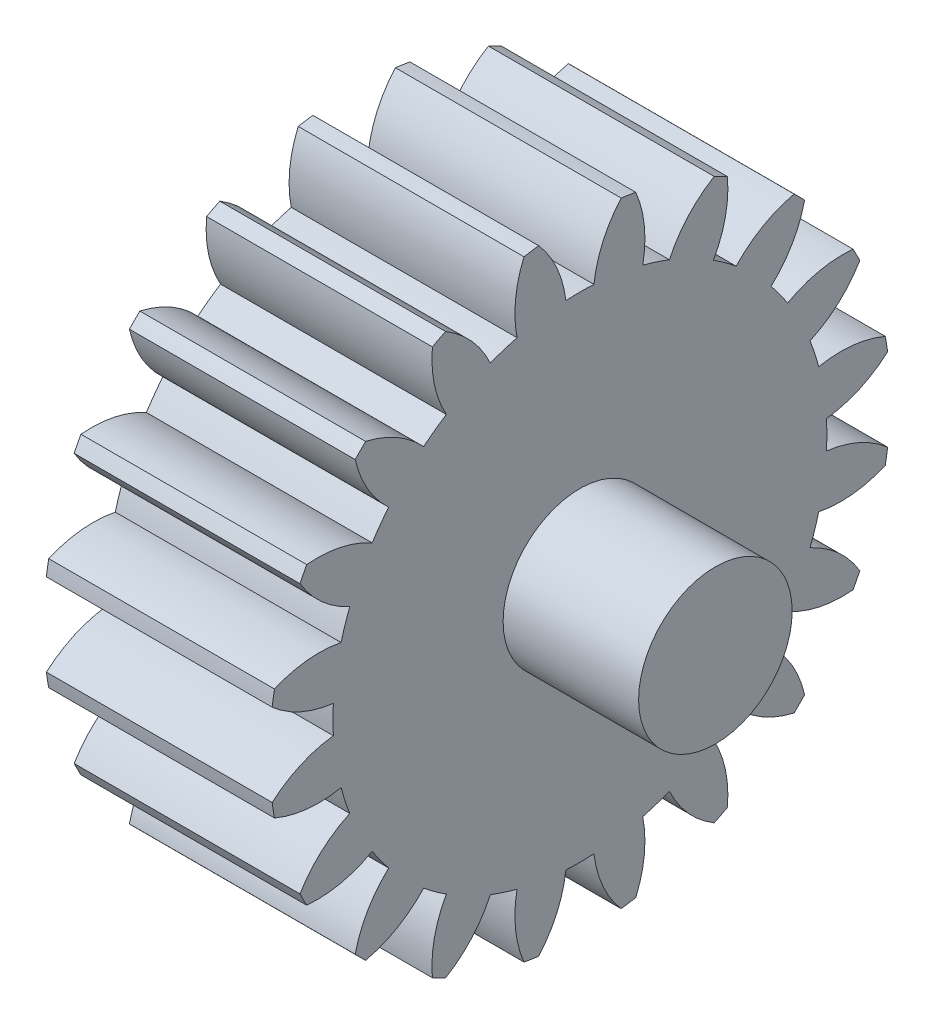
SolidWorks part; units mm, degrees
ref_plane "Plane1" through (0, 0, 0) normal (0, 0, 1) x (1, 0, 0)
ref_plane "Plane2" through (0, 0, 0) normal (0, 1, 0) x (1, 0, 0)
ref_plane "Plane3" through (0, 0, 0) normal (1, 0, 0) x (0, 0, -1)
sketch "HoldingSke" plane through (0, 0, 0) normal (0, 1, 0) x (1, 0, 0)
  line L0 (0, 0) -> (0.7518, -0.2736)
  line L1 (-15, 0) -> (100, 0) construction
  line L2 (0, 0) -> (-2.1039, 2.3779)
  line L3 (0, 0) -> (-11.863, 4.5341)
  line L4 (0, 0) -> (8.1152, 2.9537)
  line L5 (0, 0) -> (-46.8476, -17.4728)
  line L6 (0, 0) -> (-8.2896, -5.593)
  line L7 (-2.1039, 2.3779) -> (8.6586, 51.2059)
  line L8 (-76.2, 54.61) -> (-75.5, 54.61)
  line L9 (-71.009, 38.7566) -> (-53.1078, 45.2721)
  line L10 (-76.2, 71.12) -> (104.1128, 71.12)
  line L11 (0, 0) -> (-10, 0)
  line L12 (-76.2, 101.6) -> (-76.155, 101.6)
  line L13 (24.9733, 27.94) -> (52.9518, 28.4284)
  line L14 (24.9733, 27.94) -> (24.9743, 27.94)
  line L15 (24.9733, 27.94) -> (100.4006, 29.5858)
  line L16 (-63.627, -1.25) -> (-12.827, -1.25)
  circle A0 centre (0, 0) radius 2
  circle A1 centre (0, 0) radius 10.9365
  circle A2 centre (0, 0) radius 37.5
  circle A3 centre (0, 0) radius 2
  dimension "MHD" = 21.873
  dimension "Hub_dia" = 75
  dimension "Bore" = 4
  dimension "MBD" = 4
  dimension "Num_teeth" = 20
  dimension "Pitch" = 0.8
  dimension "Overall_len" = 50
  dimension "Show_teeth" = 20
  dimension "Thickness" = 10
  dimension "OAL" = 50.0001
  dimension "T_dim" = 0.7
  dimension "Ap" = 20
  dimension "H" = 19.05
  dimension "Pitch_radius" = 180.3128
  dimension "Width" = 10
  dimension "Backlash" = 0.045
  dimension "Addendum_fac" = 1
  dimension "Dedendum_fac" = 1.25
  dimension "Clearance_fac" = 0.25
  dimension "Dedendum_add" = 0.001
  dimension "Module" = 1.25
sketch "BasProSke" plane through (0, 0, 0) normal (0, 1, 0) x (1, 0, 0)
  line L0 (-10, 0) -> (60, 0) construction
  line L1 (0, 0) -> (0, 13.75)
  line L2 (0, 0) -> (10, 0)
  line L3 (10, 0) -> (10, 13.75)
  line L4 (10, 13.75) -> (0, 13.75)
  dimension "Thickness" = 10
  dimension "Diameter" = 27.5
revolve "Base-Revolve" add sketch "BasProSke" angle 360 about L0
sketch "TooCutSke" plane through (0, 0, 0) normal (1, 0, 0) x (0, 0, -1)
  line L1 (0, 0) -> (0, 107) construction
  line L2 (0, 0) -> (-1.0594, 12.455) construction
  line L3 (0, 0) -> (-3.9007, 24.6278) construction
  line L4 (-1.0594, 12.455) -> (-1.9503, 12.3139) construction
  arc A0 (0.6211, 10.9188) -> (-0.6211, 10.9188) centre (0, 0) ccw
  arc A1 (1.8466, 13.6511) -> (-1.8466, 13.6511) centre (0, 0) ccw
  circle A2 centre (0, 0) radius 12.5 construction
  circle A3 centre (0, 0) radius 11.7462 construction
  arc A4 (-0.6211, 10.9188) -> (-1.8466, 13.6511) centre (-5.5866, 10.3326) ccw
  arc A5 (1.8466, 13.6511) -> (0.6211, 10.9188) centre (5.5866, 10.3326) ccw
  dimension "Root_dia" = 21.873
  dimension "Overcut_dia" = 27.5508
  dimension "Pitch_dia" = 25
  dimension "Base_dia" = 23.4923
  dimension "Flank_rad" = 5
  dimension "Half_ang" = 9
  dimension "Half_CT" = 0.902
extrude "ToothCut" cut sketch "TooCutSke" along normal through all
fillet "Breaks" [suppressed] radius 0.025 tangent propagation no
fillet "RootFillets" [suppressed] radius 0.3135
pattern_circular "TeethCuts" count 20 every 18 about axis through (-10, 0, 0) along (1, 0, 0) of "ToothCut", "RootFillets", "Breaks"
sketch "HubNeaOneSke" plane through (0, 0, 0) normal (-1, 0, 0) x (0, 0, 1)
  circle A0 centre (0, 0) radius 10.9365
  dimension "Diameter" = 21.873
extrude "HubNearOne" [suppressed] add sketch "HubNeaOneSke" along normal blind 40.0001
sketch "HubNeaBotSke" plane through (0, 0, 0) normal (-1, 0, 0) x (0, 0, 1)
  circle A0 centre (0, 0) radius 10.9365
  dimension "Diameter" = 21.873
extrude "HubNearBoth" [suppressed] add sketch "HubNeaBotSke" along normal blind 20
ref_plane "FarPln" through (10, 0, 0) normal (1, 0, 0) x (0, 0, -1)
sketch "HubFarSke" plane through (10, 0, 0) normal (1, 0, 0) x (0, 0, -1)
  circle A0 centre (0, 0) radius 10.9365
  dimension "Diameter" = 21.873
extrude "HubFar" [suppressed] add sketch "HubFarSke" along normal blind 20
sketch "BorSke" plane through (0, 0, 0) normal (1, 0, 0) x (0, 0, -1)
  circle A0 centre (0, 0) radius 2
  dimension "Diameter" = 4
extrude "Bore" cut sketch "BorSke" along normal mid plane 100.0001
sketch "KeySke" plane through (0, 0, 0) normal (1, 0, 0) x (0, 0, -1)
  line L0 (-0.8, 0) -> (-0.8, 2.7)
  line L1 (-0.8, 2.7) -> (0.8, 2.7)
  line L2 (0.8, 2.7) -> (0.8, 0)
  line L3 (0, 0) -> (0, 34) construction
  line L4 (-0.8, 0) -> (0.8, 0)
  dimension "Offset" = 2.7
  dimension "Width" = 1.6
extrude "Keyway" [suppressed] cut sketch "KeySke" along normal mid plane 100.0001
pattern_circular "Keyway2" [suppressed] count 2 every 90 about axis through (-10, 0, 0) along (1, 0, 0) reverse direction yes
sketch "Sketch1" plane through (10, 0, 0) normal (1, 0, 0) x (0, 0, -1)
sketch "Sketch2" plane through (10, 0, 0) normal (1, 0, 0) x (0, 0, -1)
  circle A0 centre (0, 0) radius 2
extrude "Boss-Extrude1" add sketch "Sketch2" against normal blind 10
sketch "Sketch3" plane through (10, 0, 0) normal (1, 0, 0) x (0, 0, -1)
  circle A0 centre (0, 0) radius 3.4
  dimension "D1" = 6.8
extrude "Boss-Extrude2" add sketch "Sketch3" along normal blind 6
equation "' \"Module@HoldingSke\" = 6.35"
equation "' \"Num_teeth@HoldingSke\" = 12"
equation "' \"Ap@HoldingSke\" =  20"
equation "' \"Ap@HoldingSke\" = 20"
equation "' \"Width@HoldingSke\" = 0.5 * 25.4"
equation "' \"Hub_dia@HoldingSke\"= 1 * 25.4"
equation "' \"Hub_dia@HoldingSke\" = 1 * 25.4"
equation "' \"Overall_len@HoldingSke\" = 1.0 * 25.4"
equation "' \"Bore@HoldingSke\" = 0.75 * 25.4"
equation "' \"T_dim@HoldingSke\" = 0.1 * 25.4"
equation "' \"Width@KeySke\" = 0.25 * 25.4"
equation "' \"Show_teeth@HoldingSke\" = 13"
equation "' \"Backlash@HoldingSke\" = 0.009 * 25.4"
equation "' \"Addendum_fac@HoldingSke\" = 1.0"
equation "' \"Dedendum_fac@HoldingSke\" = 1.25"
equation "' \"Dedendum_add@HoldingSke\" = 0.00005 * 25.4"
equation "' \"Clearance_fac@HoldingSke\" = 0.25"
equation "\"Pitch@HoldingSke\" = 1 / \"Module@HoldingSke\""
equation "\"Overcut_dia@TooCutSke\" = (\"Num_teeth@HoldingSke\" + 2 * \"Addendum_fac@HoldingSke\") / \"Pitch@HoldingSke\" + 0.002 * 25.4"
equation "\"Pitch_dia@TooCutSke\" = \"Num_teeth@HoldingSke\" / \"Pitch@HoldingSke\""
equation "\"Base_dia@TooCutSke\" = \"Num_teeth@HoldingSke\" / \"Pitch@HoldingSke\" * cos((\"Ap@HoldingSke\"  * 3.14159265 / 180))"
equation "\"Root_dia@TooCutSke\" = (\"Num_teeth@HoldingSke\" + 2) / \"Pitch@HoldingSke\" - 2 * (\"Addendum_fac@HoldingSke\" + \"Dedendum_fac@HoldingSke\") / \"Pitch@HoldingSke\" - \"Dedendum_add@HoldingSke\" * 2"
equation "\"Half_ang@TooCutSke\" = 180 / \"Num_teeth@HoldingSke\""
equation "\"Half_CT@TooCutSke\" = \"Num_teeth@HoldingSke\" / \"Pitch@HoldingSke\" * sin((3.14159265 / 2 / \"Num_teeth@HoldingSke\")) / 2 - 7 * \"Backlash@HoldingSke\" / 4"
equation "\"Flank_rad@TooCutSke\" = \"Num_teeth@HoldingSke\" / \"Pitch@HoldingSke\" / 5"
equation "\"Radius@RootFillets\" = \"Clearance_fac@HoldingSke\" / \"Pitch@HoldingSke\" + \"Dedendum_add@HoldingSke\""
equation "\"Break_rad@Breaks\" = 0.02 / \"Pitch@HoldingSke\""
equation "\"Thickness@HoldingSke\" = \"Width@HoldingSke\""
equation "\"OAL@HoldingSke\" = \"Thickness@HoldingSke\""
equation "\"MHD@HoldingSke\" = (\"Num_teeth@HoldingSke\" + 2) / \"Pitch@HoldingSke\" - 2 * (\"Addendum_fac@HoldingSke\" + \"Dedendum_fac@HoldingSke\")  / \"Pitch@HoldingSke\" - \"Dedendum_add@HoldingSke\" * 2"
equation "\"MBD@HoldingSke\" = (\"Num_teeth@HoldingSke\" + 2) / \"Pitch@HoldingSke\" - 2 * (\"Addendum_fac@HoldingSke\" + \"Dedendum_fac@HoldingSke\")  / \"Pitch@HoldingSke\" - \"Dedendum_add@HoldingSke\" * 2 - 0.002 * 25.4"
equation "\"MHD@HoldingSke\" = ((sgn( \"MHD@HoldingSke\" - \"Hub_dia@HoldingSke\" )-1)*( \"MHD@HoldingSke\" - \"Hub_dia@HoldingSke\" ))/-2+ \"Hub_dia@HoldingSke\""
equation "\"MBD@HoldingSke\" = ((sgn( \"MBD@HoldingSke\" - \"Bore@HoldingSke\" )-1)*( \"MBD@HoldingSke\" - \"Bore@HoldingSke\" ))/-2+ \"Bore@HoldingSke\""
equation "\"OAL@HoldingSke\" = ((sgn( \"OAL@HoldingSke\" - \"Overall_len@HoldingSke\" )+1)*( \"OAL@HoldingSke\" - \"Overall_len@HoldingSke\" ))/2 + \"Overall_len@HoldingSke\" + 0.000002 * 25.4"
equation "\"Num_teeth@TeethCuts\" = int( \"Show_teeth@HoldingSke\" ) + 1"
equation "\"Num_teeth@TeethCuts\" = ((sgn( \"Num_teeth@TeethCuts\" - \"Num_teeth@HoldingSke\" )-1)*( \"Num_teeth@TeethCuts\" - \"Num_teeth@HoldingSke\" ))/-2+ \"Num_teeth@HoldingSke\""
equation "\"Num_teeth@TeethCuts\" = ((sgn( \"Num_teeth@TeethCuts\" - 2.0)+1)*( \"Num_teeth@TeethCuts\" - 2.0))/2 +2.0"
equation "\"Angle@TeethCuts\" = 360.0 / \"Num_teeth@HoldingSke\""
equation "\"Diameter@BasProSke\" = (\"Num_teeth@HoldingSke\" + 2 * \"Addendum_fac@HoldingSke\") / \"Pitch@HoldingSke\""
equation "\"Thickness@BasProSke\"  = \"Thickness@HoldingSke\""
equation "' \"Fillet_rad@BasProSke\" =  \"Thickness@HoldingSke\" * 0.05"
equation "' \"Fillet_rad@BasProSke\" = \"Thickness@HoldingSke\" * 0.05"
equation "\"MHD@HoldingSke\" = ((sgn( \"MHD@HoldingSke\" - \"Root_dia@TooCutSke\" )-1)*( \"MHD@HoldingSke\" - \"Root_dia@TooCutSke\" ))/-2+ \"Root_dia@TooCutSke\""
equation "\"Diameter@HubNeaOneSke\" = \"MHD@HoldingSke\""
equation "\"Length@HubNearOne\" = \"OAL@HoldingSke\" - \"Thickness@BasProSke\""
equation "\"Diameter@HubNeaBotSke\" = \"MHD@HoldingSke\""
equation "\"Length@HubNearBoth\" = ( \"OAL@HoldingSke\" - \"Thickness@BasProSke\" ) / 2.0"
equation "\"Thickness@FarPln\" = \"Thickness@BasProSke\""
equation "\"Diameter@HubFarSke\" = \"MHD@HoldingSke\""
equation "\"Length@HubFar\" = ( \"OAL@HoldingSke\" - \"Thickness@BasProSke\" ) / 2.0"
equation "\"Diameter@BorSke\" = \"MBD@HoldingSke\""
equation "\"D1@Bore\" = \"OAL@HoldingSke\" * 2.0"
equation "\"D1@Keyway\" = \"OAL@HoldingSke\" * 2.0"
equation "\"Offset@KeySke\" = \"T_dim@HoldingSke\" + \"MBD@HoldingSke\" / 2.0"
